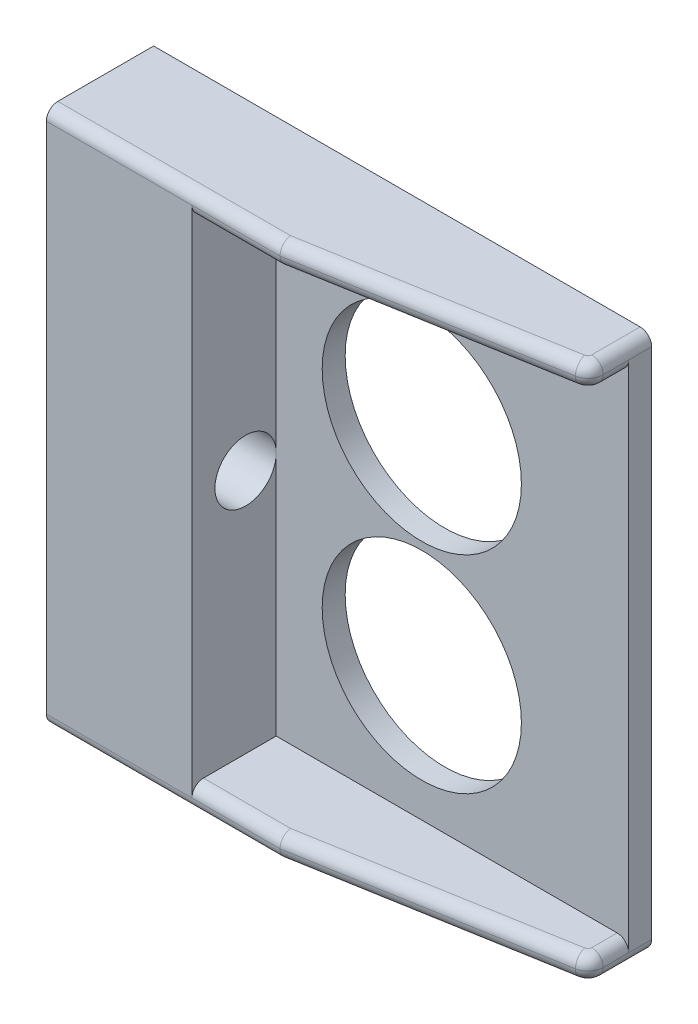
SolidWorks part; units mm, degrees
ref_plane "Plan de face" through (0, 0, 0) normal (0, 0, 1) x (1, 0, 0)
ref_plane "Plan de dessus" through (0, 0, 0) normal (0, 1, 0) x (1, 0, 0)
ref_plane "Plan de droite" through (0, 0, 0) normal (1, 0, 0) x (0, 0, -1)
sketch "Sketch1" plane through (0, 0, 0) normal (0, 0, 1) x (1, 0, 0)
  line L1 (-32.5, -35) -> (32.5, -35)
  line L2 (-32.5, -35) -> (-32.5, 35)
  line L3 (-32.5, 35) -> (32.5, 35)
  line L4 (32.5, -35) -> (32.5, 35)
  point P4 (-32.5, 0)
  point P5 (0, 35)
  dimension "D1" = 70
  dimension "D2" = 65
extrude "Boss-Extrude1" add sketch "Sketch1" along normal blind 3
sketch "Sketch2" plane through (-2.5, 35, 0) normal (0, 1, 0) x (0, 0, -1)
  line L0 (-14, -0.5) -> (-14, 30)
  line L1 (-3, -35) -> (-3, 30)
  line L3 (-3, 30) -> (-14, 30)
  line L4 (-3, -2.5) -> (0, -2.5) construction
  line L5 (-8, -35) -> (-14, -0.5)
  line L7 (-3, -0.5) -> (-14, -0.5) construction
  line L9 (-3, -35) -> (-8, -35)
  dimension "D1" = 5
  dimension "D2" = 34.5
  dimension "D3" = 30.5
  dimension "D4" = 11
extrude "Boss-Extrude2" add sketch "Sketch2" against normal blind 3
pattern_linear "LPattern1" count 2 spacing 67 along (0, -1, 0) of "Boss-Extrude2"
sketch "Sketch4" plane through (0, 32, 0) normal (0, -1, 0) x (1, 0, 0)
  line L0 (-32.5, 14) -> (-2, 14) construction
  line L1 (-32.5, 3) -> (-13.5, 3)
  line L2 (-32.5, 3) -> (-32.5, 14)
  line L3 (-32.5, 14) -> (-13.5, 14)
  line L4 (-13.5, 3) -> (-13.5, 14)
  dimension "D1" = 19
extrude "Boss-Extrude3" add sketch "Sketch4" along normal up to next
fillet "Fillet4" radius 2 2 edges at (32.5, 33.5, 8) (32.5, -33.5, 8)
fillet "Fillet3" radius 1.5 16 edges at (14.4213, 32, 11.1441) (14.4213, 35, 11.1441) (-17.25, 35, 14) (-7.75, 32, 14) (14.4213, -32, 11.1441) (-7.75, -32, 14) (-17.25, -35, 14) (14.4213, -35, 11.1441) (32.5, 32, 4.6589) (32.0306, 32, 7.6052) (32.5, 35, 3.1589) (32.0306, 35, 7.6052) (32.5, -32, 4.6589) (32.0306, -32, 7.6052) (32.5, -35, 3.1589) (32.0306, -35, 7.6052)
sketch "Sketch10" plane through (-32.5, 0, 0) normal (-1, 0, 0) x (0, 0, 1)
  point P0 (7, 0)
  dimension "D1" = 7
hole_wizard "Ø8.0mm Dowel Hole1" positions "Sketch10" profile "Sketch8" hole size "Ø8.0" standard "ISO" end condition through all
sketch "Sketch8" plane through (-32.5, 0, 7) normal (0, 1, 0) x (0, 0, 1)
  line L0 (0, 0) -> (0, 65)
  line L1 (0, 65) -> (4, 65)
  line L2 (4, 65) -> (4, 0.025)
  line L3 (4, 0.025) -> (4.025, 0)
  line L5 (4.025, 0) -> (0, 0)
  line L6 (-4, 0.025) -> (-4.025, 0) construction
  line L11 (0, -6.35) -> (0, 107.95) construction
  dimension "Thru Hole Dia." = 8
  dimension "Thru Hole Depth" = 65
  dimension "Near C'Sink Dia." = 8.05
  dimension "Near C'Sink Angle" = 90
cosmetic thread "Cosmetic Thread1" parameters "D1"=13.5, "D2"=9.5
sketch "Sketch13" plane through (0, 0, 3) normal (0, 0, 1) x (1, 0, 0)
  line L2 (30.5857, -35) -> (-2.1295, -35) construction
  line L3 (32.5, -33.5) -> (32.5, 33.5) construction
  point P7 (5.5, -14.5)
  dimension "D1" = 20.5
  dimension "D2" = 27
hole_wizard "Ø1.0 (26) Diameter Hole1" positions "Sketch13" profile "Sketch14" hole size "Ø1.0" standard "ISO" end condition through all
sketch "Sketch14" plane through (5.5, -14.5, 3) normal (1, 0, 0) x (0, -1, 0)
  line L0 (0, 0) -> (0, 3)
  line L1 (0, 3) -> (13, 3)
  line L2 (13, 3) -> (13, 0)
  line L5 (13, 0) -> (0, 0)
  line L11 (0, -6.35) -> (0, 107.95) construction
  dimension "Thru Hole Dia." = 26
  dimension "Thru Hole Depth" = 3
pattern_linear "LPattern2" count 2 spacing 27 along (0, 1, 0) of "Ø1.0 (26) Diameter Hole1"
